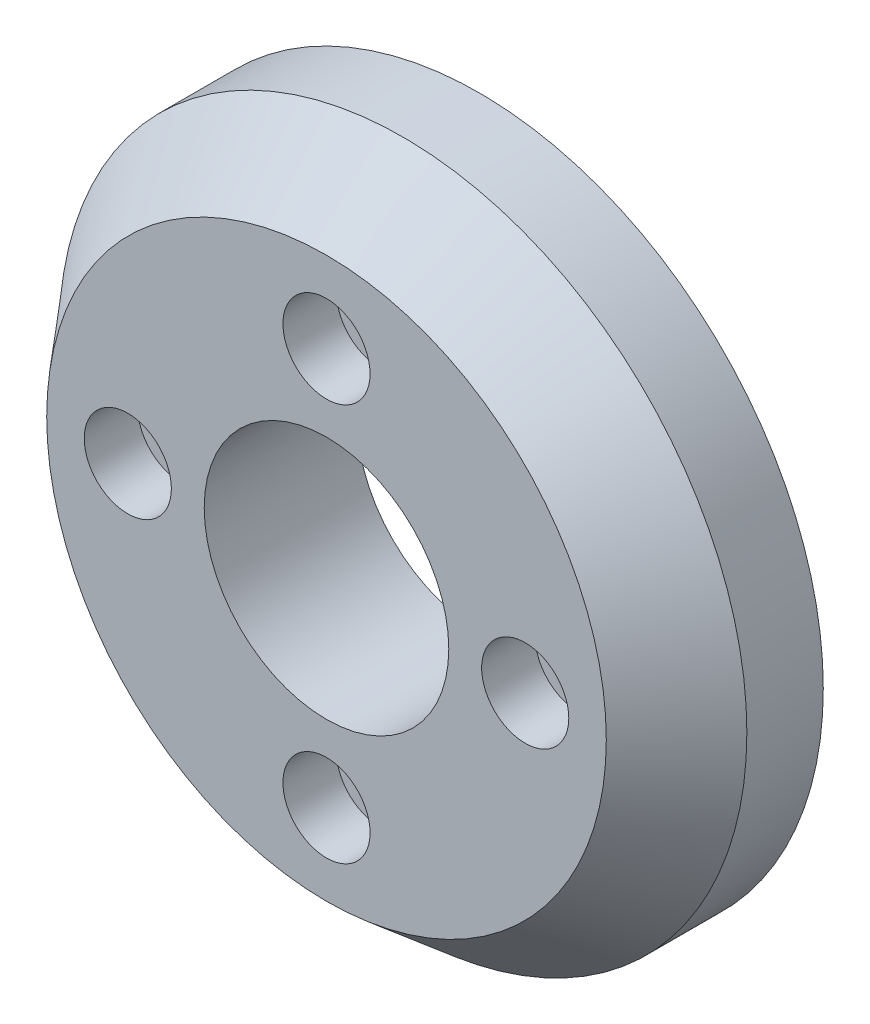
SolidWorks part; units mm, degrees
ref_plane "Front Plane" through (0, 0, 0) normal (1, 0, 0) x (0, 1, 0)
ref_plane "Top Plane" through (0, 0, 0) normal (0, 0, 1) x (0, 1, 0)
ref_plane "Right Plane" through (0, 0, 0) normal (0, 1, 0) x (-1, 0, 0)
sketch "Sketch1" plane through (0, 0, 0) normal (0, 0, 1) x (0, 1, 0)
  circle A0 centre (0, 0) radius 22.5
  circle A1 centre (0, 0) radius 13 construction
  circle A2 centre (0, 13) radius 2.85
  circle A3 centre (0, 13) radius 1.6
  circle A4 centre (13, 0) radius 2.85
  circle A5 centre (13, 0) radius 1.6
  circle A6 centre (0, -13) radius 2.85
  circle A7 centre (0, -13) radius 1.6
  circle A8 centre (-13, 0) radius 2.85
  circle A9 centre (-13, 0) radius 1.6
  point P19 (0, 0)
  dimension "D1" = 45
  dimension "D2" = 26
  dimension "D3" = 5.7
  dimension "D4" = 3.2
  dimension "D5" = 4
extrude "Boss-Extrude1" add sketch "Sketch1" along normal blind 10 contours A0 A8 A6 A4 A2 region at (0, 0, 0)
extrude "Boss-Extrude2" add sketch "Sketch1<3>" along normal offset from surface (6.5 mm away) 3.5 contours A8 A9 | A2 A3 | A4 A5 | A6 A7 region at (-13, -2.7694, 0) region at (0, 10.2306, 0) region at (13, -2.7694, 0) region at (0, -15.7694, 0) up to face at (2.85, -13, 10)
sketch "Sketch1<3>" plane through (0, 0, 0) normal (0, 0, 1) x (0, 1, 0) same geometry as "Sketch1"
chamfer "Chamfer1" distance 5 angle 40 1 edges at (22.5, 0, 10) first distance on face at (22.5, 0, 10)
sketch "Sketch2" plane through (0, 0, 10) normal (0, 0, 1) x (1, 0, 0)
  circle A0 centre (0, 0) radius 8
  dimension "D1" = 16
extrude "Cut-Extrude1" cut sketch "Sketch2" against normal through all both and the other way through all
